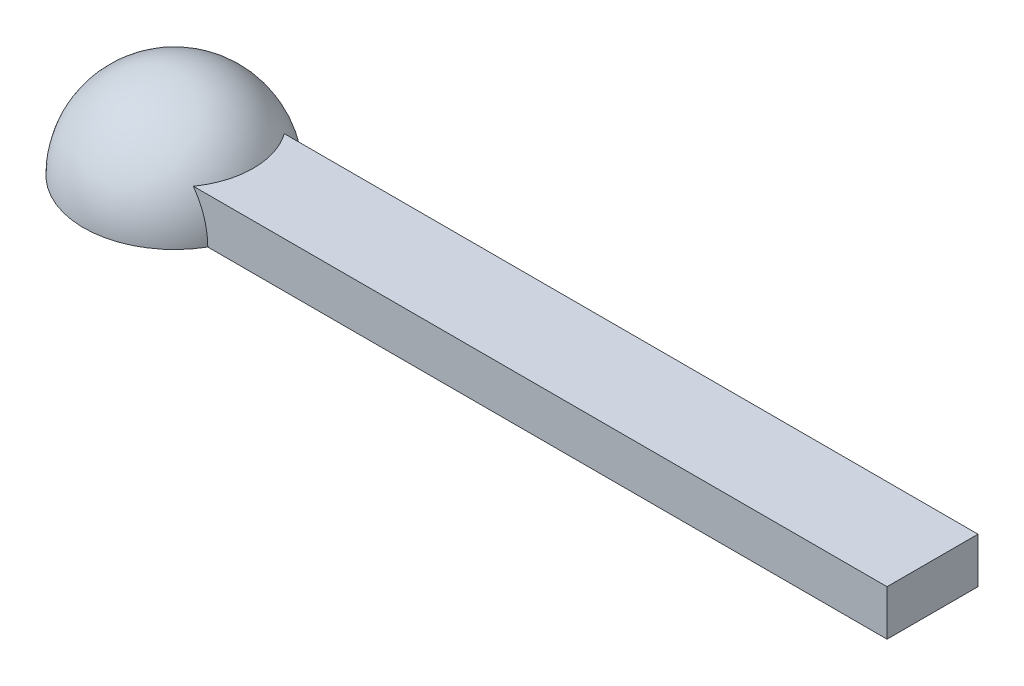
SolidWorks part; units mm, degrees
ref_plane "Front Plane" through (0, 0, 0) normal (0, 0, 1) x (1, 0, 0)
ref_plane "Top Plane" through (0, 0, 0) normal (0, 1, 0) x (1, 0, 0)
ref_plane "Right Plane" through (0, 0, 0) normal (1, 0, 0) x (0, 0, -1)
sketch "Sketch1" plane through (0, 0, 0) normal (0, 1, 0) x (1, 0, 0)
  line L0 (-6, 0) -> (-5, 0)
  line L1 (5, 0) -> (6, 0)
  arc A0 (6, 0) -> (-6, 0) centre (0, 0) ccw
  arc A1 (5, 0) -> (-5, 0) centre (0, 0) ccw
revolve "Revolve1" add sketch "Sketch1" angle 180 about L0
ref_plane "Plane1" through (10, 0, 0) normal (1, 0, 0) x (0, 0, -1)
sketch "Sketch2" plane through (10, 0, 0) normal (1, 0, 0) x (0, 0, -1)
  line L1 (-3, 3) -> (3, 3)
  line L2 (-3, 3) -> (-3, 0)
  line L3 (-3, 0) -> (3, 0)
  line L4 (3, 3) -> (3, 0)
  point P4 (0, 0)
  dimension "D1" = 3
  dimension "D2" = 6
extrude "Boss-Extrude1" add sketch "Sketch2" against normal up to surface and the other way blind 40 up to face at (0, 0, -6)
